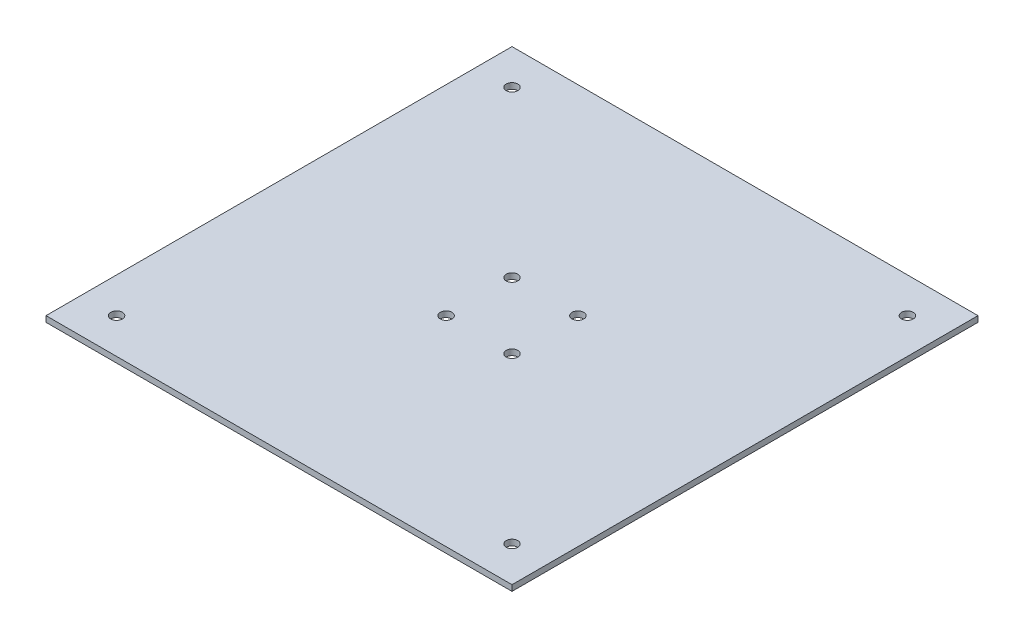
SolidWorks part; units mm, degrees
material "6061 Alloy"
ref_plane "Front Plane" through (0, 0, 0) normal (0, 0, 1) x (1, 0, 0)
ref_plane "Top Plane" through (0, 0, 0) normal (0, 1, 0) x (1, 0, 0)
ref_plane "Right Plane" through (0, 0, 0) normal (1, 0, 0) x (0, 0, -1)
sketch "Sketch1" plane through (0, 0, 0) normal (0, 1, 0) x (1, 0, 0)
  line L1 (0, 0) -> (127, 0)
  line L2 (0, 0) -> (0, 127)
  line L3 (0, 127) -> (127, 127)
  line L4 (127, 0) -> (127, 127)
  dimension "width" = 127
sheet metal parameters "Sheet-Metal1" thickness 1.5875 parameters "D1"=0.7366
base flange "Base-Flange1" sketch "Sketch1" thickness 1.5875 reverse thickness direction yes parameters "D1"=0.7366
sketch "Sketch4" plane through (0, 1.5875, 0) normal (0, 1, 0) x (1, 0, 0)
  line L0 (0, 0) -> (127, 127)
  line L1 (127, 0) -> (0, 127)
  circle A0 centre (54.5197, 54.5197) radius 1.5875
  circle A1 centre (9.6185, 9.6185) radius 1.5875
  circle A2 centre (9.6185, 117.3815) radius 1.5875
  circle A3 centre (54.5197, 72.4803) radius 1.5875
  circle A4 centre (117.3815, 117.3815) radius 1.5875
  circle A5 centre (72.4803, 72.4803) radius 1.5875
  circle A6 centre (117.3815, 9.6185) radius 1.5875
  circle A7 centre (72.4803, 54.5197) radius 1.5875
  point P12 (63.5, 63.5)
  dimension "D1" = 12.7
  dimension "hole_dia" = 3.175
  dimension "D2" = 63.5
extrude "Extrude1" cut sketch "Sketch4" against normal up to surface (1.5875 mm away) contours A0 | A1 | A7 | A6 | A5 | A3 | A2 | A4 normal cut yes up to face at (63.5, 0, -63.5)
flat pattern "Flat-Pattern1" [suppressed]
sketch "Bend-Lines1" plane through (0, 0, 0) normal (0, 1, 0) x (-1, 0, 0)
